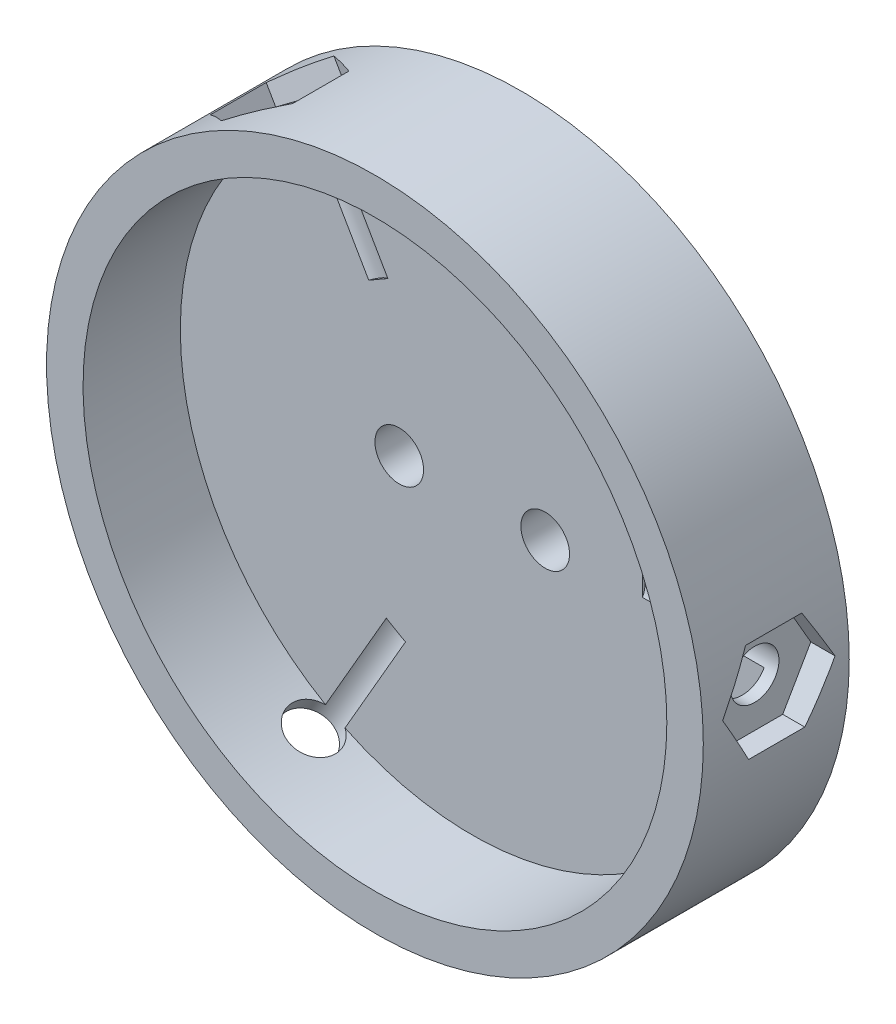
SolidWorks part; units mm, degrees
ref_plane "Front Plane" through (0, 0, 0) normal (0, 0, 1) x (1, 0, 0)
ref_plane "Top Plane" through (0, 0, 0) normal (0, 1, 0) x (1, 0, 0)
ref_plane "Right Plane" through (0, 0, 0) normal (1, 0, 0) x (0, 0, -1)
sketch "Sketch1" plane through (0, 0, 0) normal (0, 0, 1) x (1, 0, 0)
  circle A0 centre (0, 0) radius 13.5
  dimension "D1" = 27
extrude "Boss-Extrude1" add sketch "Sketch1" along normal blind 2
sketch "Sketch2" plane through (0, 0, 2) normal (0, 0, 1) x (1, 0, 0)
  circle A0 centre (0, 0) radius 13.5 construction
  circle A1 centre (0, 0) radius 13.5
  circle A2 centre (0, 0) radius 12
  dimension "D1" = 1.5
extrude "Boss-Extrude2" add sketch "Sketch2" along normal blind 4
sketch "Sketch3" plane through (0, 0, 0) normal (1, 0, 0) x (0, 0, -1)
  line L0 (-6, 13.5) -> (-6, -13.5) construction
  line L1 (-5.2, 0.4166) -> (-4.0453, -1.5834)
  line L2 (-4.0453, -1.5834) -> (-1.7359, -1.5834)
  line L3 (-1.7359, -1.5834) -> (-0.5812, 0.4166)
  line L4 (-0.5812, 0.4166) -> (-1.7359, 2.4166)
  line L5 (-1.7359, 2.4166) -> (-4.0453, 2.4166)
  line L6 (-4.0453, 2.4166) -> (-5.2, 0.4166)
  circle A0 centre (-2.8906, 0.4166) radius 2 construction
  circle A1 centre (-2.8906, 0.4166) radius 1
  dimension "D1" = 4
  dimension "D2" = 0.8
ref_plane "Plane1" through (20, 0, 0) normal (1, 0, 0) x (0, 0, -1)
sketch "Sketch4" plane through (20, 0, 0) normal (1, 0, 0) x (0, 0, -1)
  line L1 (-0.5812, 0.4166) -> (-1.7359, 2.4166)
  line L2 (-1.7359, 2.4166) -> (-4.0453, 2.4166)
  line L3 (-4.0453, 2.4166) -> (-5.2, 0.4166)
  line L4 (-5.2, 0.4166) -> (-4.0453, -1.5834)
  line L5 (-4.0453, -1.5834) -> (-1.7359, -1.5834)
  line L6 (-1.7359, -1.5834) -> (-0.5812, 0.4166)
  circle A0 centre (-2.8906, 0.4166) radius 1
  circle A1 centre (-2.8906, 0.4166) radius 2 construction
extrude "Cut-Extrude1" cut sketch "Sketch4" against normal blind 13 contours A0 region at (20, 0.4166, 2.8906)
extrude "Cut-Extrude2" cut sketch "Sketch4<3>" against normal blind 7.5
sketch "Sketch4<3>" plane through (20, 0, 0) normal (1, 0, 0) x (0, 0, -1) same geometry as "Sketch4"
pattern_circular "CirPattern1" count 3 over 360 about axis through (0, 0, 2) along (0, 0, -1) of "Cut-Extrude2"
pattern_circular "CirPattern2" count 3 over 360 about axis through (0, 0, 2) along (0, 0, -1) of "CirPattern1", "Cut-Extrude1"
sketch "Sketch5" plane through (0, 0, 2) normal (0, 0, 1) x (1, 0, 0)
  line L0 (-5.1216, 0) -> (5.2928, 0) construction
  line L1 (0, 2.4166) -> (0, 0.4166) construction
  circle A0 centre (3, 0) radius 1
  circle A1 centre (-3, 0) radius 1
  dimension "D1" = 3
  dimension "D2" = 3
extrude "Cut-Extrude3" cut sketch "Sketch5" against normal through all
